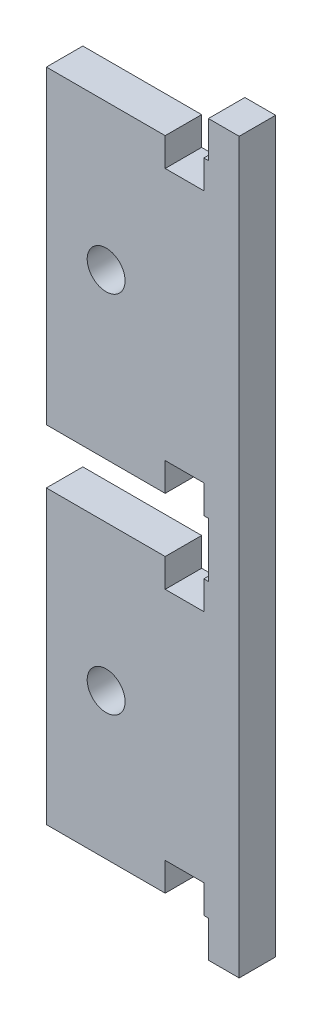
SolidWorks part; units mm, degrees
material "AISI 4130 Steel, annealed at 865C"
ref_plane "X-Y Datum" through (0, 0, 0) normal (0, 0, 1) x (1, 0, 0)
ref_plane "X-Z Datum" through (0, 0, 0) normal (0, 1, 0) x (1, 0, 0)
ref_plane "Y-Z Datum" through (0, 0, 0) normal (1, 0, 0) x (0, 0, -1)
sketch "Sketch2" plane through (0, 0, 0) normal (0, 0, 1) x (1, 0, 0)
  line L0 (32.9006, 127) -> (0, 127) construction
  line L1 (0, 0) -> (40.64, 0)
  line L2 (0, 0) -> (0, 127)
  line L3 (0, 127) -> (40.64, 127)
  line L4 (40.64, 0) -> (40.64, 127)
  point P7 (17.4625, 31.75)
  point P8 (17.4625, 95.25)
  dimension "D1" = 40.64
extrude "Boss-Extrude1" add sketch "Sketch2" along normal blind 6.35
hole_wizard "M6 Clearance Hole1" positions "Sketch3" profile "Sketch4" hole size "M6" standard "ANSI Metric" end condition through all
sketch "Sketch3" plane through (0, 0, 6.35) normal (0, 0, 1) x (1, 0, 0)
  point P0 (17.4625, 31.75)
  point P3 (17.4625, 95.25)
sketch "Sketch4" plane through (17.4625, 31.75, 6.35) normal (1, 0, 0) x (0, -1, 0)
  line L0 (0, 0) -> (0, 6.35)
  line L1 (0, 6.35) -> (3.3, 6.35)
  line L2 (3.3, 6.35) -> (3.3, 0)
  line L5 (3.3, 0) -> (0, 0)
  line L11 (0, -6.35) -> (0, 107.95) construction
  dimension "Thru Hole Dia." = 6.6
  dimension "Thru Hole Depth" = 6.35
sketch "Sketch5" plane through (0, 0, 6.35) normal (0, 0, 1) x (1, 0, 0)
  line L0 (7.0505, 127) -> (7.0505, 0)
  line L1 (40.64, 127) -> (0, 127) construction
  line L2 (0, 0) -> (40.64, 0) construction
  circle A0 centre (17.4625, 95.25) radius 3.3 construction
  point P6 (14.1625, 95.25)
  line M4 (0, 127) -> (0, 0)
  line M5 (0, 0) -> (40.64, 0)
  line M7 (40.64, 127) -> (0, 127)
  dimension "D1" = 7.112
extrude "Cut-Extrude1" cut sketch "Sketch5" against normal through all and the other way through all contours L0 M7 M4 M5 region at (3.5253, 63.5, 6.35)
sketch "Sketch6" plane through (0, 0, 6.35) normal (0, 0, 1) x (1, 0, 0)
  line L0 (-3.175, 120.65) -> (36.0756, 120.65)
  line L1 (36.0756, 120.65) -> (36.0756, 130.175)
  line L2 (36.0756, 130.175) -> (-3.175, 130.175)
  line L3 (-3.175, 130.175) -> (-3.175, 120.65)
  line L4 (0, 123.825) -> (32.9006, 123.825)
  line L5 (32.9006, 123.825) -> (32.9006, 127)
  line L6 (32.9006, 127) -> (0, 127)
  line L7 (0, 127) -> (0, 123.825)
  line L8 (0, 123.825) -> (32.9006, 123.825)
  line L9 (32.9006, 123.825) -> (32.9006, 127)
  line L10 (32.9006, 127) -> (0, 127)
  line L11 (0, 127) -> (0, 123.825)
  line L16 (0, 60.325) -> (32.9006, 60.325)
  line L17 (32.9006, 60.325) -> (32.9006, 63.5)
  line L18 (32.9006, 63.5) -> (0, 63.5)
  line L19 (0, 63.5) -> (0, 60.325)
  line L24 (0, 0) -> (34.925, 0)
  line L25 (34.925, 0) -> (34.925, 3.175)
  line L26 (34.925, 3.175) -> (0, 3.175)
  line L27 (0, 3.175) -> (0, 0)
  line L28 (36.0756, 66.675) -> (-3.175, 66.675)
  line L29 (-3.175, 66.675) -> (-3.175, 57.15)
  line L30 (-3.175, 57.15) -> (36.0756, 57.15)
  line L31 (36.0756, 57.15) -> (36.0756, 66.675)
  line L32 (38.1, 6.35) -> (-3.175, 6.35)
  line L33 (-3.175, 6.35) -> (-3.175, -3.175)
  line L34 (-3.175, -3.175) -> (38.1, -3.175)
  line L35 (38.1, -3.175) -> (38.1, 6.35)
  line L36 (35.2819, 127) -> (35.2819, 0)
  line L37 (40.64, 127) -> (7.0505, 127) construction
  line L38 (7.0505, 0) -> (40.64, 0) construction
  line M19 (7.0505, 127) -> (7.0505, 0)
  line M20 (7.0505, 0) -> (40.64, 0)
  line M22 (40.64, 127) -> (7.0505, 127)
  dimension "D5" = 2.3813
  dimension "D1" = 0
  dimension "D4" = 3.175
extrude "Cut-Extrude2" cut sketch "Sketch6" against normal through all contours L36 L9 L8 L0 M22 M19 | L8 L9 M22 M19 | L36 L28 L18 L17 L16 L30 M19 | L17 L18 L16 M19 | L36 L32 L26 L25 M19 M20 | L25 L26 M19 M20 region at (22.1716, 122.4845, 6.35) region at (19.9756, 125.4125, 6.35) region at (21.1662, 66.3771, 6.35) region at (19.9756, 61.9125, 6.35) region at (21.3402, 4.7229, 6.35) region at (20.9878, 1.5875, 6.35)
sketch "Sketch7" plane through (0, 0, 6.35) normal (0, 0, 1) x (1, 0, 0)
  line L0 (34.4805, 115.697) -> (27.7495, 115.697)
  line L5 (27.7495, 120.8405) -> (27.7495, 115.697)
  line L18 (34.29, 120.65) -> (27.94, 120.65)
  line L19 (34.29, 120.65) -> (34.29, 115.8875)
  line L20 (34.29, 115.8875) -> (27.94, 115.8875)
  line L21 (27.94, 120.65) -> (27.94, 115.8875)
  line L22 (34.29, 71.4375) -> (27.94, 71.4375)
  line L23 (34.29, 71.4375) -> (34.29, 66.675)
  line L24 (34.29, 66.675) -> (27.94, 66.675)
  line L25 (27.94, 71.4375) -> (27.94, 66.675)
  line L26 (34.29, 57.15) -> (27.94, 57.15)
  line L27 (34.29, 57.15) -> (34.29, 52.3875)
  line L28 (34.29, 52.3875) -> (27.94, 52.3875)
  line L29 (27.94, 57.15) -> (27.94, 52.3875)
  line L30 (34.29, 11.1125) -> (27.94, 11.1125)
  line L31 (34.29, 11.1125) -> (34.29, 6.35)
  line L32 (34.29, 6.35) -> (27.94, 6.35)
  line L33 (27.94, 11.1125) -> (27.94, 6.35)
  line L34 (34.4805, 120.8405) -> (27.7495, 120.8405)
  line L35 (34.4805, 120.8405) -> (34.4805, 115.697)
  line L36 (34.4805, 66.4845) -> (27.7495, 66.4845)
  line L37 (27.7495, 71.628) -> (27.7495, 66.4845)
  line L38 (34.4805, 71.628) -> (27.7495, 71.628)
  line L39 (34.4805, 71.628) -> (34.4805, 66.4845)
  line L40 (34.4805, 52.197) -> (27.7495, 52.197)
  line L41 (27.7495, 57.3405) -> (27.7495, 52.197)
  line L42 (34.4805, 57.3405) -> (27.7495, 57.3405)
  line L43 (34.4805, 57.3405) -> (34.4805, 52.197)
  line L44 (34.4805, 6.1595) -> (27.7495, 6.1595)
  line L45 (27.7495, 11.303) -> (27.7495, 6.1595)
  line L46 (34.4805, 11.303) -> (27.7495, 11.303)
  line L47 (34.4805, 11.303) -> (34.4805, 6.1595)
  line L48 (35.2819, 6.35) -> (7.0505, 6.35) construction
  line M4 (35.2819, 120.65) -> (7.0505, 120.65)
  line M6 (7.0505, 66.675) -> (35.2819, 66.675)
  line M8 (35.2819, 57.15) -> (7.0505, 57.15)
  line M10 (7.0505, 6.35) -> (35.2819, 6.35)
  dimension "D1" = 0.1905
extrude "Cut-Extrude3" cut sketch "Sketch7" against normal through all contours L30 L33 L31 M10 | L47 L46 L45 L33 L30 L31 M10 | L47 L45 L44 M10 | L29 L28 L27 M8 | L43 L27 L28 L29 L41 L40 M8 | L43 L42 L41 M8 | L39 L37 L36 M6 | L22 L25 L23 M6 | L39 L38 L37 L25 L22 L23 M6 | L21 L20 L19 M4 | L35 L19 L20 L21 L5 L0 M4 | L35 L34 L5 M4 region at (31.115, 115.7806, 6.35) region at (31.115, 120.7453, 6.35) region at (31.115, 118.2688, 6.35) region at (31.115, 69.0563, 6.35) region at (31.115, 71.5211, 6.35) region at (31.115, 66.5798, 6.35) region at (31.115, 54.7688, 6.35) region at (34.3853, 57.0664, 6.35) region at (31.115, 57.2453, 6.35) region at (31.115, 8.7312, 6.35) region at (31.115, 11.1961, 6.35) region at (31.115, 6.2547, 6.35)
